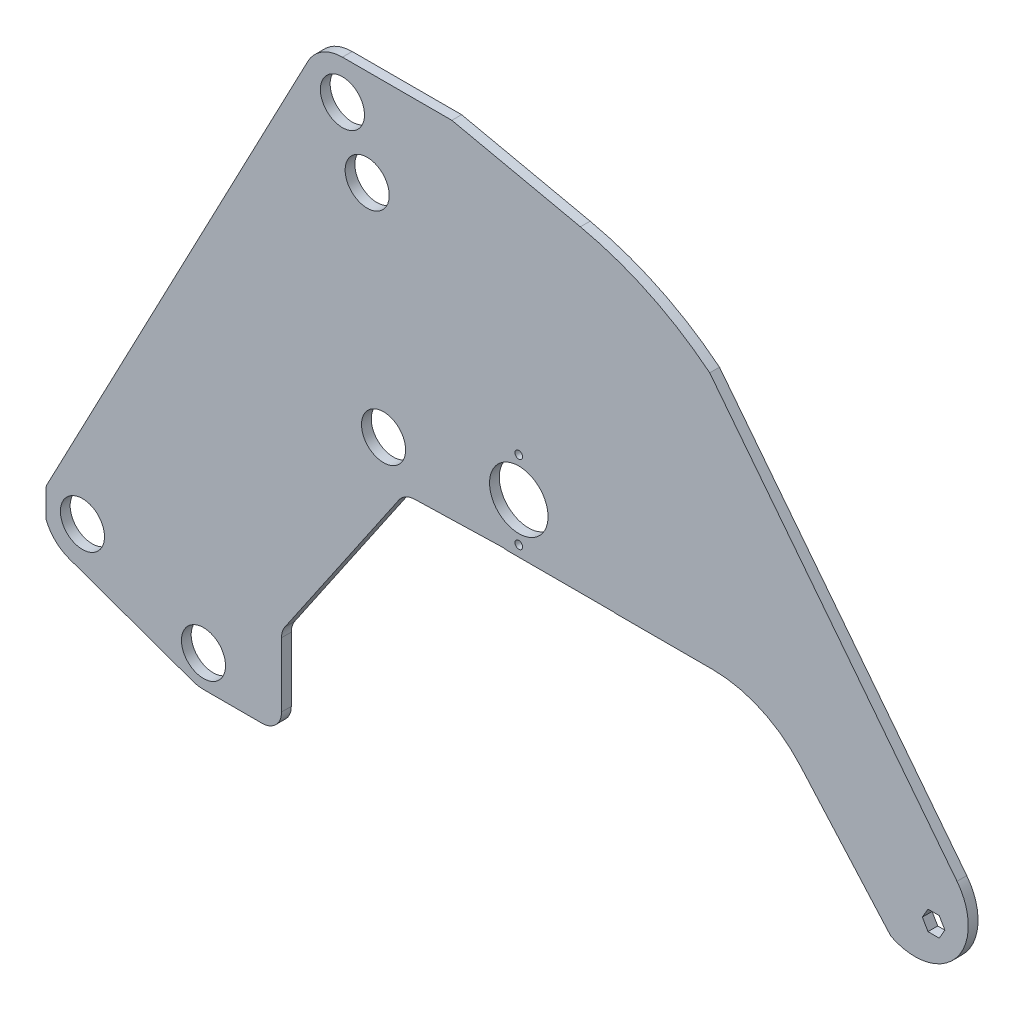
SolidWorks part; units mm, degrees
ref_plane "Front Plane" through (0, 0, 0) normal (0, 0, 1) x (1, 0, 0)
ref_plane "Top Plane" through (0, 0, 0) normal (0, 1, 0) x (1, 0, 0)
ref_plane "Right Plane" through (0, 0, 0) normal (1, 0, 0) x (0, 0, -1)
sketch "Model" plane through (0, 0, 0) normal (0, 0, 1) x (1, 0, 0)
  line L0 (71.3681, -9.525) -> (71.3681, 43.162)
  line L1 (-201.9337, 106.0953) -> (-145.2781, 107.6333)
  line L2 (-286.27, -8.1018) -> (-212.0775, 100.5612)
  line L3 (-288.4816, -57.15) -> (-288.4816, -15.2631)
  line L4 (-271.3307, 318.2291) -> (-440.5556, -4.1587)
  line L5 (-441.7893, -6.8892) -> (-441.7893, -25.0386)
  line L6 (-138.7956, 106.0563) -> (-87.5941, 77.7906)
  line L7 (-426.6215, -39.8795) -> (-346.2033, -68.6492)
  line L8 (-81.0319, 66.6723) -> (-81.0319, -9.525)
  line L9 (-339.2816, -69.85) -> (-301.1816, -69.85)
  line L10 (-68.3319, -22.225) -> (58.6681, -22.225)
  line L11 (67.226, 52.5456) -> (-231.7249, 325.1911)
  circle A0 centre (-68.3319, 42.418) radius 2.4892
  arc A1 (-440.5556, -4.1587) -> (-441.7893, -6.8892) centre (-418.0657, -15.9639) ccw
  arc A2 (-231.7249, 325.1911) -> (-271.3307, 318.2291) centre (-248.8407, 306.4239) ccw
  circle A3 centre (-134.0441, 114.3) radius 2.4892
  circle A4 centre (58.6681, -14.732) radius 2.4892
  arc A5 (71.3681, 43.162) -> (67.226, 52.5456) centre (58.6681, 43.162) ccw
  circle A6 centre (-68.3319, 42.418) radius 2.4892
  arc A7 (58.6681, -22.225) -> (71.3681, -9.525) centre (58.6681, -9.525) ccw
  arc A8 (-201.9337, 106.0953) -> (-212.0775, 100.5612) centre (-201.5891, 93.3999) ccw
  circle A9 centre (-339.2816, -49.3014) radius 14.351
  circle A10 centre (-418.0657, -15.9639) radius 14.351
  arc A11 (-138.7956, 106.0563) -> (-145.2781, 107.6333) centre (-144.9335, 94.938) ccw
  circle A12 centre (-222.0793, 130.9577) radius 14.351
  arc A13 (-286.27, -8.1018) -> (-288.4816, -15.2631) centre (-275.7816, -15.2631) ccw
  arc A14 (-81.0319, 66.6723) -> (-87.5941, 77.7906) centre (-93.7319, 66.6723) ccw
  circle A15 centre (-134.0441, 139.7) radius 19.05
  circle A16 centre (-68.3319, -14.732) radius 2.4892
  arc A17 (-346.2033, -68.6492) -> (-339.2816, -69.85) centre (-339.2816, -49.3014) ccw
  arc A18 (-81.0319, -9.525) -> (-68.3319, -22.225) centre (-68.3319, -9.525) ccw
  arc A19 (-301.1816, -69.85) -> (-288.4816, -57.15) centre (-301.1816, -57.15) ccw
  arc A20 (-441.7893, -25.0386) -> (-426.6215, -39.8795) centre (-418.0657, -15.9639) ccw
  circle A21 centre (-134.0441, 165.1) radius 2.4892
  circle A22 centre (-232.7296, 269.0861) radius 14.351
  circle A23 centre (-248.8407, 306.4239) radius 14.351
  circle A24 centre (58.6681, 42.418) radius 2.4892
  point P57 (0, 0)
extrude "Boss-Extrude1" add sketch "Model" along normal blind 6.35 contours L5 A20 L7 A17 L9 A19 L3 A13 L2 A8 L1 A11 L6 A14 L8 A18 L10 A7 L0 A5 L11 A2 L4 A1 A24 A23 A22 A21 A0 A3 A4 A9 A10 A12 A15 A16 region at (-205.056, 109.2877, 0)
sketch "Sketch2" plane through (0, 0, 6.35) normal (0, 0, 1) x (1, 0, 0)
  line L0 (71.3681, 107.1397) -> (-71.7385, 107.1397)
  line L1 (71.3681, -9.525) -> (71.3681, 43.162) construction
  line L2 (-81.0319, 66.6723) -> (-81.0319, -9.525) construction
  line L3 (-71.7385, 107.1397) -> (-71.9304, 107.3369)
  line L4 (-71.9304, 107.3369) -> (-156.1988, 107.3369)
  line L5 (-201.9337, 106.0953) -> (-145.2781, 107.6333) construction
  line L6 (-156.1988, 107.3369) -> (-81.0319, 31.3512)
  line L7 (-81.0319, 31.3512) -> (-101.7139, -22.9499)
  line L8 (-101.7139, -22.9499) -> (74.4539, -33.7593)
  line L9 (71.3681, -33.57) -> (71.3681, 107.1397)
  point P12 (20.6958, 20.8155)
  point P15 (-71.9304, 107.3369)
  point P16 (21.6365, 11.243)
  circle M6 centre (-68.3319, 42.418) radius 2.4892
  circle M8 centre (58.6681, -14.732) radius 2.4892
  circle M13 centre (-68.3319, -14.732) radius 2.4892
  arc M25 (-145.2781, 107.6333) -> (-138.7956, 106.0563) centre (-144.9335, 94.938) cw
  line M26 (-138.7956, 106.0563) -> (-87.5941, 77.7906)
  arc M27 (-87.5941, 77.7906) -> (-81.0319, 66.6723) centre (-93.7319, 66.6723) cw
  line M28 (-81.0319, 66.6723) -> (-81.0319, -9.525)
  arc M29 (-81.0319, -9.525) -> (-68.3319, -22.225) centre (-68.3319, -9.525) ccw
  line M30 (-68.3319, -22.225) -> (58.6681, -22.225)
  arc M31 (58.6681, -22.225) -> (71.3681, -9.525) centre (58.6681, -9.525) ccw
  line M32 (71.3681, -9.525) -> (71.3681, 43.162)
extrude "Cut-Extrude1" cut sketch "Sketch2" against normal blind 6.35 contours L3 L4 L0 M25 M26 M27 M28 M29 M30 M31 M32 M6 M8 M13 region at (-9.471, 45.3981, 6.35)
sketch "Sketch3" plane through (0, 0, 6.35) normal (0, 0, 1) x (1, 0, 0)
  line L5 (-93.9522, 313.6342) -> (-177.6296, 331.8239)
  line L6 (26.3573, 107.1397) -> (28.8954, 104.344)
  line L7 (-9.789, 273.4325) -> (151.1775, 67.2749)
  line L8 (28.8954, 104.344) -> (108.0842, 14.8362)
  line L10 (-177.6296, 331.8239) -> (-248.8407, 331.8239)
  line L11 (-248.8407, 331.8239) -> (7.3645, 107.1397)
  line L12 (7.3645, 107.1397) -> (26.3573, 107.1397)
  arc A2 (-9.789, 273.4325) -> (-93.9522, 313.6342) centre (-137.1155, 115.0715) ccw
  arc A3 (108.0842, 14.8362) -> (151.1775, 67.2749) centre (123.7678, 45.8737) ccw
  arc A4 (-231.7249, 325.1911) -> (-271.3307, 318.2291) centre (-248.8407, 306.4239) ccw construction
  dimension "D2" = 203.2
extrude "Boss-Extrude2" add sketch "Sketch3" against normal blind 6.35
fillet "Fillet1" radius 76.2 1 edges at (26.3573, 107.1397, 3.175)
sketch "Sketch4" plane through (0, 0, 6.35) normal (0, 0, 1) x (1, 0, 0)
  line L1 (143.2922, 35.7915) -> (139.626, 42.1415)
  line L2 (139.626, 42.1415) -> (132.2936, 42.1415)
  line L3 (132.2936, 42.1415) -> (128.6275, 35.7915)
  line L4 (128.6275, 35.7915) -> (132.2936, 29.4415)
  line L5 (132.2936, 29.4415) -> (139.626, 29.4415)
  line L6 (139.626, 29.4415) -> (143.2922, 35.7915)
  circle A1 centre (135.9598, 35.7915) radius 6.35 construction
  point P0 (135.9598, 35.7915)
  dimension "D2" = 12.7
extrude "Cut-Extrude2" cut sketch "Sketch4" against normal blind 6.35
